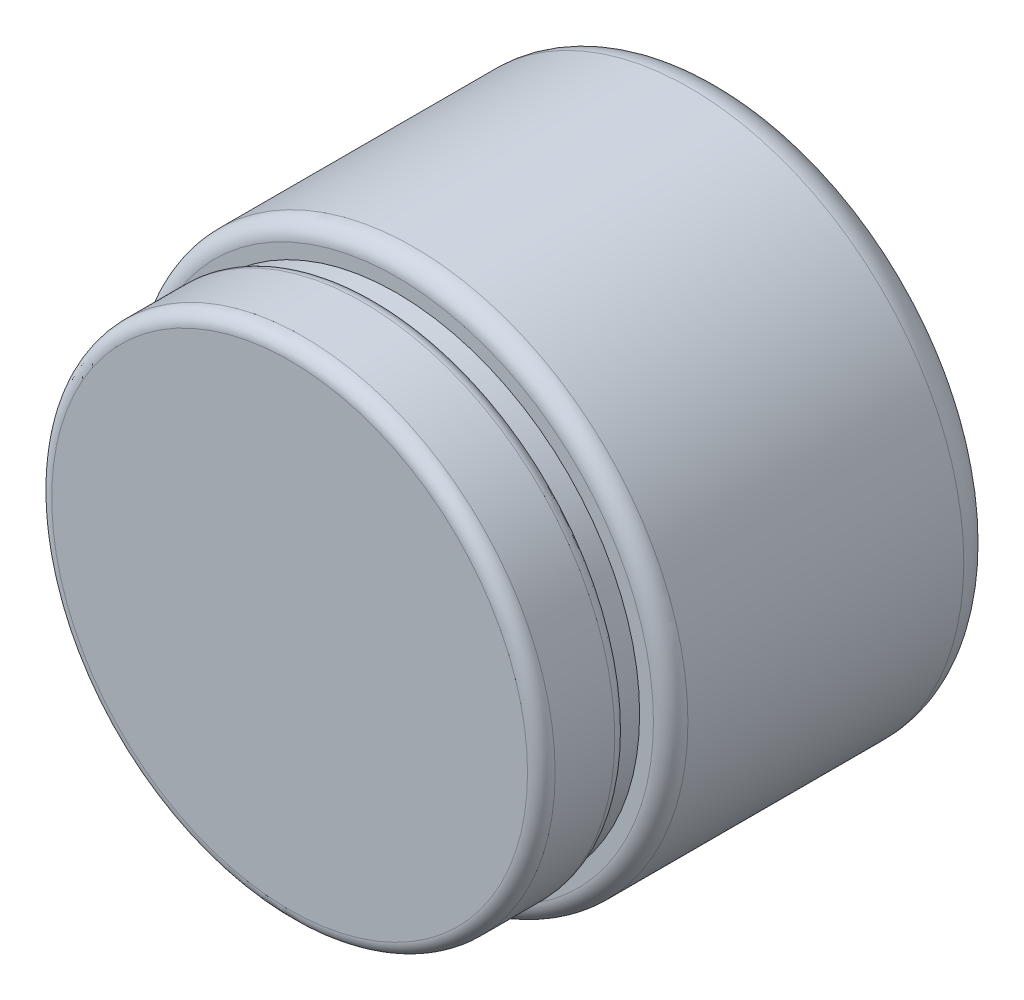
SolidWorks part; units mm, degrees
ref_plane "Front Plane" through (0, 0, 0) normal (0, 0, 1) x (1, 0, 0)
ref_plane "Top Plane" through (0, 0, 0) normal (0, 1, 0) x (1, 0, 0)
ref_plane "Right Plane" through (0, 0, 0) normal (1, 0, 0) x (0, 0, -1)
sketch "Sketch1" plane through (0, 0, 0) normal (0, 0, 1) x (1, 0, 0)
  circle A0 centre (0, 0) radius 37.084
  dimension "D1" = 74.168
extrude "Boss-Extrude1" add sketch "Sketch1" along normal blind 12.7
sketch "Sketch2" plane through (0, 0, 0) normal (0, 0, -1) x (-1, 0, 0)
  circle A0 centre (0, 0) radius 35.814
  dimension "D1" = 71.628
extrude "Boss-Extrude2" add sketch "Sketch2" along normal blind 3.048
sketch "Sketch3" plane through (0, 0, -3.048) normal (0, 0, -1) x (-1, 0, 0)
  circle A0 centre (0, 0) radius 40.386
  dimension "D1" = 80.772
extrude "Boss-Extrude3" add sketch "Sketch3" along normal blind 48.26
fillet "Fillet1" radius 2.54 1 edges at (-40.386, 0, -3.048)
fillet "Fillet2" radius 5.08 1 edges at (-40.386, 0, -51.308)
fillet "Fillet3" radius 2.032 2 edges at (37.084, 0, 0) (37.084, 0, 12.7)
